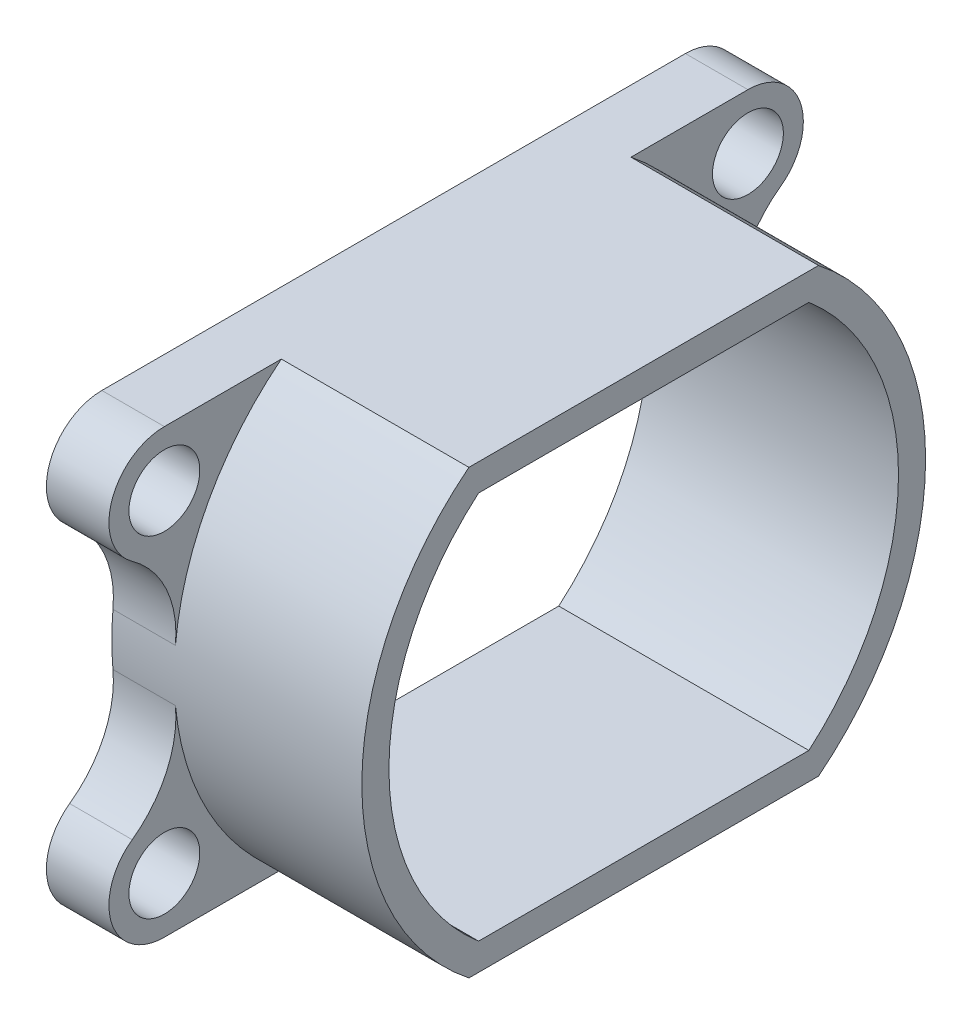
SolidWorks part; units mm, degrees
ref_plane "Front Plane" through (0, 0, 0) normal (0, 0, 1) x (1, 0, 0)
ref_plane "Top Plane" through (0, 0, 0) normal (0, 1, 0) x (1, 0, 0)
ref_plane "Right Plane" through (0, 0, 0) normal (1, 0, 0) x (0, 0, -1)
sketch "Sketch1" plane through (0, 0, 0) normal (1, 0, 0) x (0, 0, -1)
  line L0 (-7.8677, -9.16) -> (7.8677, -9.16) construction
  line L1 (-7.8677, 9.16) -> (7.8677, 9.16) construction
  line L2 (-7.8677, -9.16) -> (7.8677, 9.16) construction
  line L3 (-7.8677, 9.16) -> (7.8677, -9.16) construction
  line L4 (-7.923, 9.31) -> (7.923, 9.31)
  line L5 (-7.923, -9.31) -> (7.923, -9.31)
  line L6 (-8.3877, 10.61) -> (8.3877, 10.61)
  line L7 (-8.3877, -10.61) -> (8.3877, -10.61)
  arc A0 (-7.8677, 9.16) -> (-7.8677, -9.16) centre (0, 0) ccw construction
  arc A1 (7.8677, -9.16) -> (7.8677, 9.16) centre (0, 0) ccw construction
  arc A2 (7.923, -9.31) -> (7.923, 9.31) centre (0, 0) ccw
  arc A3 (-7.923, 9.31) -> (-7.923, -9.31) centre (0, 0) ccw
  arc A4 (8.3877, -10.61) -> (8.3877, 10.61) centre (0, 0) ccw
  arc A5 (-8.3877, 10.61) -> (-8.3877, -10.61) centre (0, 0) ccw
  point P0 (0, 0)
  dimension "D2" = 24.15
  dimension "D1" = 18.32
  dimension "D3" = 0.15
  dimension "D4" = 1.3
extrude "Motor Holder" add sketch "Sketch1" along normal blind 12
sketch "Sketch2" plane through (0, 0, 0) normal (-1, 0, 0) x (0, 0, 1)
  line L4 (0, 0) -> (0, 27.8421) construction
  line L5 (0, 0) -> (-9.5877, 0) construction
  line L7 (8.3877, 10.61) -> (14, 10.61)
  line L24 (14.9133, 5.4517) -> (12.7028, 4.6436)
  line L25 (14.9133, -5.4517) -> (12.7028, -4.6436)
  line L26 (8.3877, -10.61) -> (14, -10.61)
  line L27 (-8.3877, -10.61) -> (-14, -10.61)
  line L28 (-14.9133, -5.4517) -> (-12.7028, -4.6436)
  line L29 (-14.9133, 5.4517) -> (-12.7028, 4.6436)
  line L30 (-8.3877, 10.61) -> (-14, 10.61)
  circle A10 centre (14, 7.95) radius 1.7
  circle A12 centre (-14, 7.95) radius 1.7
  circle A13 centre (14, -7.95) radius 1.7
  circle A14 centre (-14, -7.95) radius 1.7
  arc A16 (-8.3877, 10.61) -> (-8.3877, -10.61) centre (0, 0) ccw construction
  arc A20 (14, 10.61) -> (14.9133, 5.4517) centre (14, 7.95) cw
  arc A21 (8.3877, 10.61) -> (12.7028, 4.6436) centre (0, 0) cw
  arc A22 (-8.3877, 10.61) -> (-8.3877, -10.61) centre (0, 0) ccw
  arc A31 (-8.3877, 10.61) -> (-8.3877, -10.61) centre (0, 0) ccw
  arc A32 (8.3877, -10.61) -> (8.3877, 10.61) centre (0, 0) ccw construction
  arc A33 (14, -10.61) -> (14.9133, -5.4517) centre (14, -7.95) ccw
  arc A34 (8.3877, -10.61) -> (12.7028, -4.6436) centre (0, 0) ccw
  arc A35 (-8.3877, -10.61) -> (-12.7028, -4.6436) centre (0, 0) cw
  arc A36 (-14, -10.61) -> (-14.9133, -5.4517) centre (-14, -7.95) cw
  arc A37 (-14, 10.61) -> (-14.9133, 5.4517) centre (-14, 7.95) ccw
  arc A38 (-8.3877, 10.61) -> (-12.7028, 4.6436) centre (0, 0) ccw
  arc M11 (8.3877, -10.61) -> (8.3877, 10.61) centre (0, 0) ccw
  arc M13 (-8.3877, 10.61) -> (-8.3877, -10.61) centre (0, 0) ccw
  dimension "D2" = 3.4
  dimension "D1" = 7.95
  dimension "D3" = 14
extrude "Boss-Extrude1" add sketch "Sketch2" against normal blind 3 contours L30 A37 L29 A12 M13 | A36 L27 L28 A14 M13 | L26 A33 L25 A13 M11 | A20 L7 L24 A10 M11 region at (0, -5.1435, 13.773) region at (0, 10.508, 11.1939) region at (0, 5.1435, -13.773) region at (0, -10.508, -11.1939)
fillet "Fillet1" radius 5 4 edges at (1.5, -4.6436, -12.7028) (1.5, 4.6436, -12.7028) (1.5, -4.6436, 12.7028) (1.5, 4.6436, 12.7028)
